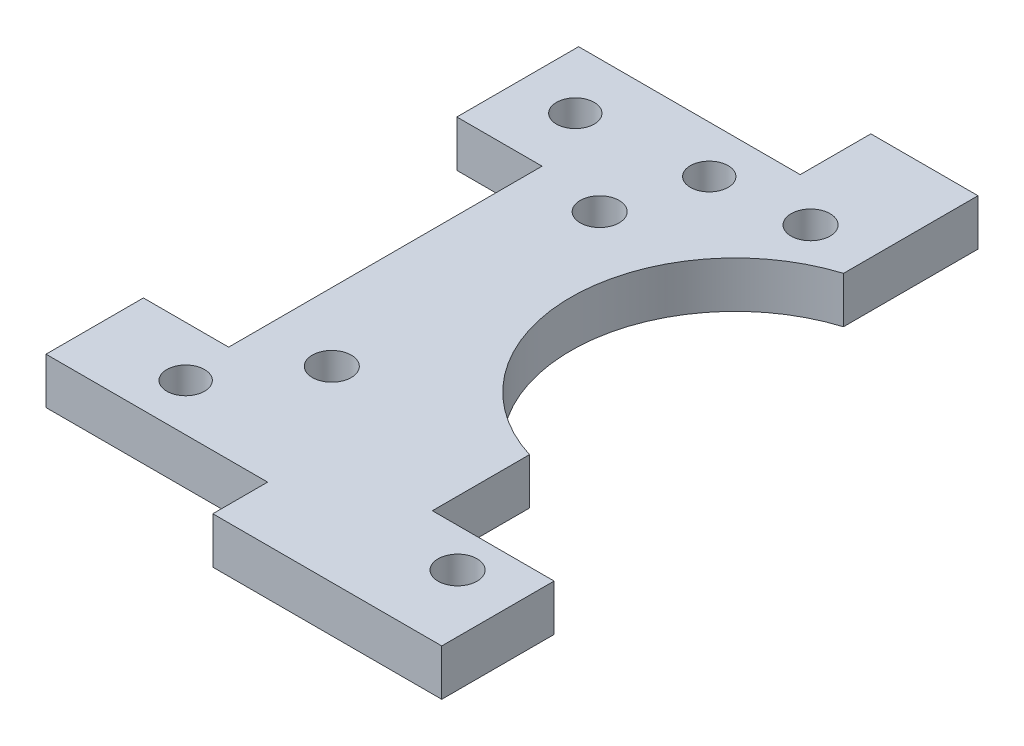
SolidWorks part; units mm, degrees
ref_plane "前视基准面" through (0, 0, 0) normal (0, 0, 1) x (1, 0, 0)
ref_plane "上视基准面" through (0, 0, 0) normal (0, 1, 0) x (1, 0, 0)
ref_plane "右视基准面" through (0, 0, 0) normal (1, 0, 0) x (0, 0, -1)
other "Configuration Table"
sketch "草图1" plane through (0, 0, 0) normal (0, 1, 0) x (1, 0, 0)
  line L1 (0, 0) -> (20, 0)
  line L2 (0, 0) -> (0, 35.74)
  line L3 (0, 35.74) -> (20, 35.74)
  line L4 (20, 0) -> (20, 35.74)
  dimension "D1" = 35.74
  dimension "D2" = 20
extrude "凸台-拉伸1" add sketch "草图1" along normal blind 3.8
sketch "草图2" plane through (0, 0, 0) normal (0, -1, 0) x (1, 0, 0)
  line L0 (20, 0) -> (20, -35.74) construction
  line L1 (20, 0) -> (11.2, 0)
  line L2 (20, 0) -> (20, 8.5)
  line L3 (20, 8.5) -> (11.2, 8.5)
  line L4 (11.2, 0) -> (11.2, 8.5)
  line L5 (20, -35.74) -> (0, -35.74) construction
  line L6 (20, -35.74) -> (11.2, -35.74)
  line L7 (20, -35.74) -> (20, -45.54)
  line L8 (20, -45.54) -> (11.2, -45.54)
  line L9 (11.2, -35.74) -> (11.2, -45.54)
  line L10 (0, 0) -> (20, 0) construction
  dimension "D1" = 8.8
  dimension "D2" = 8.8
  dimension "D3" = 8.5
  dimension "D4" = 0
  dimension "D5" = 9.8
extrude "凸台-拉伸2" add sketch "草图2" against normal blind 3.8
sketch "草图3" plane through (0, 0, 0) normal (0, -1, 0) x (-1, 0, 0)
  line L0 (-20, -8.5) -> (-11.2, -8.5) construction
  line L1 (-20, -8.5) -> (-20, 45.54) construction
  circle A0 centre (-24, 21.6) radius 13.5
  dimension "D3" = 27
  dimension "D1" = 30.1
  dimension "D2" = 4
extrude "切除-拉伸1" cut sketch "草图3" against normal blind 3.8
sketch "草图4" plane through (0, 0, 0) normal (0, -1, 0) x (-1, 0, 0)
  line L1 (-19.8, 1.75) -> (-10.4, 1.75)
  line L2 (-19.8, 1.75) -> (-19.8, -3.25)
  line L3 (-19.8, -3.25) -> (-10.4, -3.25)
  line L4 (-10.4, 1.75) -> (-10.4, -3.25)
  line L7 (-20, -8.5) -> (-11.2, -8.5) construction
  line L8 (-20, -8.5) -> (-20, 8.7062) construction
  dimension "D1" = 5
  dimension "D2" = 9.4
  dimension "D3" = 5.25
  dimension "D4" = 0.2
extrude "切除-拉伸2" cut sketch "草图4" against normal blind 1
sketch "草图5" plane through (20, 0, 0) normal (1, 0, 0) x (0, 0, -1)
  line L0 (-8.5, 3.8) -> (-8.5, 0) construction
  line L1 (-8.5, 0) -> (0.729, 0)
  line L2 (-8.5, 0) -> (-8.5, 3.8)
  line L3 (-8.5, 3.8) -> (0.729, 3.8)
  line L4 (0.729, 0) -> (0.729, 3.8)
  line L5 (-8.5, 0) -> (8.7062, 0) construction
  line L6 (-8.5, 3.8) -> (8.7062, 3.8) construction
extrude "凸台-拉伸3" add sketch "草图5" along normal blind 10
sketch "草图6" plane through (0, 0, 0) normal (0, -1, 0) x (-1, 0, 0)
  line L0 (-11.2, 35.74) -> (-11.2, 45.54) construction
  line L1 (-11.2, 45.54) -> (-20, 45.54) construction
  line L2 (-30, -8.5) -> (-11.2, -8.5) construction
  line L3 (-11.2, -8.5) -> (-11.2, -3.25) construction
  circle A0 centre (-15.2, 36.59) radius 1.6
  circle A1 centre (-25.25, -2.45) radius 1.6
  dimension "D1" = 4
  dimension "D2" = 8.95
  dimension "D3" = 3.2
  dimension "D4" = 6.05
  dimension "D5" = 14.05
  dimension "D6" = 3.2
extrude "切除-拉伸3" cut sketch "草图6" against normal blind 10
sketch "草图7" plane through (0, 0, 0) normal (0, -1, 0) x (-1, 0, 0)
  line L0 (0, 35.74) -> (0, 0) construction
  line L1 (-11.2, 35.74) -> (0, 35.74) construction
  circle A0 centre (-5.6, 28.87) radius 1.6
  circle A1 centre (-5.6, 6.87) radius 1.6
  point P6 (0, 17.87)
  point P9 (-5.6, 35.74)
  dimension "D1" = 3.2
  dimension "D2" = 3.2
  dimension "D3" = 11
  dimension "D4" = 11
  dimension "D5" = 0
  dimension "D6" = 0
extrude "切除-拉伸4" cut sketch "草图7" against normal through all
sketch "草图8" plane through (0, 0, 0) normal (0, -1, 0) x (1, 0, 0)
  line L0 (11.2, -35.74) -> (11.2, -45.54) construction
  line L1 (0, -35.74) -> (11.2, -35.74)
  line L2 (0, -35.74) -> (0, -39.74)
  line L3 (0, -39.74) -> (11.2, -39.74)
  line L4 (11.2, -35.74) -> (11.2, -39.74)
  line L5 (11.2, 8.5) -> (11.2, 3.25) construction
  line L6 (0, 0) -> (11.2, 0)
  line L7 (0, 0) -> (0, 4)
  line L8 (0, 4) -> (11.2, 4)
  line L9 (11.2, 0) -> (11.2, 4)
  dimension "D1" = 4
  dimension "D2" = 4
extrude "凸台-拉伸4" add sketch "草图8" against normal up to surface (3.8 mm away) up to face at (5.6, 3.8, -30.47)
sketch "草图9" plane through (0, 0, 0) normal (0, -1, 0) x (-1, 0, 0)
  circle A0 centre (-7.6, 35.87) radius 1.55
  circle A1 centre (-0.6, -0.13) radius 1.55
  circle A2 centre (-5.6, 6.87) radius 1.6 construction
  circle A3 centre (-5.6, 28.87) radius 1.6 construction
  dimension "D1" = 3.1
  dimension "D2" = 3.1
  dimension "D3" = 7
  dimension "D4" = 7
  dimension "D5" = 2
  dimension "D6" = 5
extrude "切除-拉伸5" cut sketch "草图9" against normal through all
sketch "草图10" plane through (0, 0, 0) normal (-1, 0, 0) x (0, 0, 1)
  line L0 (-39.74, 0) -> (-45.54, 0) construction
  line L1 (-39.74, 0) -> (-29.74, 0)
  line L2 (-39.74, 0) -> (-39.74, 3.8)
  line L3 (-39.74, 3.8) -> (-29.74, 3.8)
  line L4 (-29.74, 0) -> (-29.74, 3.8)
  line L5 (-39.74, 3.8) -> (-39.74, 0) construction
  line L6 (-39.74, 3.8) -> (-1.2992, 3.8) construction
  line L7 (-39.74, 0) -> (-1.2992, 0) construction
  line L8 (4, 3.8) -> (-4, 3.8)
  line L9 (4, 3.8) -> (4, 0)
  line L10 (4, 0) -> (-4, 0)
  line L11 (-4, 3.8) -> (-4, 0)
  dimension "D1" = 10
  dimension "D2" = 8
extrude "凸台-拉伸5" add sketch "草图10" along normal blind 7
sketch "草图11" plane through (0, 0, 0) normal (0, -1, 0) x (-1, 0, 0)
  circle A0 centre (2.4, 34.87) radius 1.55
  circle A1 centre (-7.6, 35.87) radius 1.55 construction
  dimension "D1" = 3.1
  dimension "D2" = 10
  dimension "D3" = 1
extrude "切除-拉伸6" cut sketch "草图11" against normal blind 8
sketch "草图12" plane through (0, 0, 0) normal (0, -1, 0) x (-1, 0, 0)
  line L1 (-11.2, -3.25) -> (-6.2, -3.25)
  line L2 (-11.2, -3.25) -> (-11.2, 1.75)
  line L3 (-11.2, 1.75) -> (-6.2, 1.75)
  line L4 (-6.2, -3.25) -> (-6.2, 1.75)
  dimension "D1" = 5
extrude "切除-拉伸7" cut sketch "草图12" against normal up to surface (1 mm away) up to face at (13.8, 1, 0.5)
sketch "草图13" plane through (0, 0, 0) normal (0, -1, 0) x (-1, 0, 0)
  circle A0 centre (-0.6, -0.13) radius 1.55
extrude "切除-拉伸8" cut sketch "草图13" against normal blind 5
